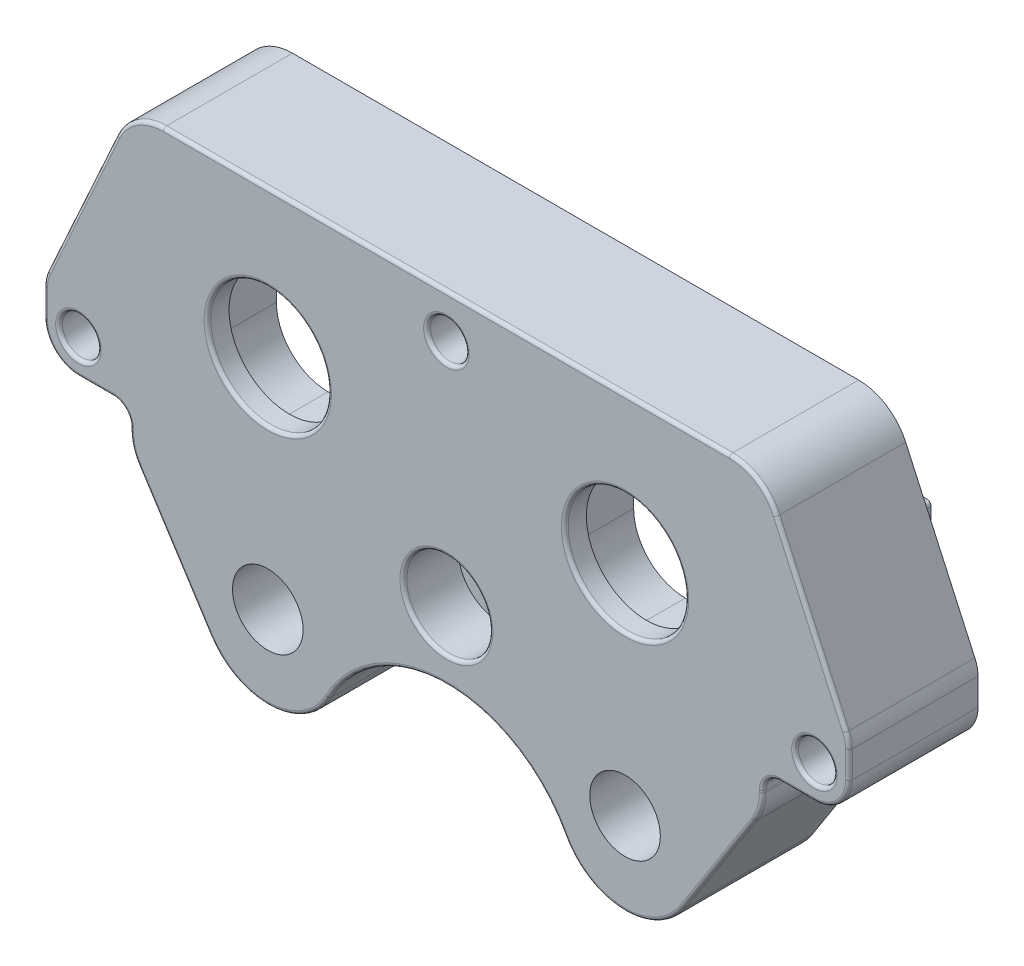
SolidWorks part; units mm, degrees
ref_plane "Front Plane" through (0, 0, 0) normal (0, 0, 1) x (1, 0, 0)
ref_plane "Top Plane" through (0, 0, 0) normal (0, 1, 0) x (1, 0, 0)
ref_plane "Right Plane" through (0, 0, 0) normal (1, 0, 0) x (0, 0, -1)
sketch "Sketch1" plane through (0, 0, 0) normal (0, 0, 1) x (1, 0, 0)
  line L0 (55.5, 15) -> (27.5, 15)
  line L1 (14, 15) -> (-14, 15)
  line L2 (14, 15) -> (14, -15)
  line L3 (14, -15) -> (-14, -15)
  line L4 (-14, 15) -> (-14, -15)
  line L5 (14, 15) -> (-14, -15) construction
  line L6 (14, -15) -> (-14, 15) construction
  line L7 (-16.75, -42) -> (16.75, -42)
  line L8 (-16.75, -42) -> (-16.75, 16)
  line L9 (-16.75, 16) -> (16.75, 16)
  line L10 (16.75, -42) -> (16.75, 16)
  line L11 (55.5, 15) -> (55.5, -15)
  line L12 (55.5, -15) -> (27.5, -15)
  line L13 (27.5, 15) -> (27.5, -15)
  line L14 (55.5, 15) -> (27.5, -15) construction
  line L15 (55.5, -15) -> (27.5, 15) construction
  line L16 (24.75, -42) -> (58.25, -42)
  line L17 (24.75, -42) -> (24.75, 16)
  line L18 (24.75, 16) -> (58.25, 16)
  line L19 (58.25, -42) -> (58.25, 16)
  circle A0 centre (0, 0) radius 19.05 construction
  circle A1 centre (41.5, 0) radius 19.05 construction
  circle A2 centre (20.75, -14.6491) radius 6.35 construction
  circle A3 centre (20.75, -14.6491) radius 41.275 construction
  circle A4 centre (0, 0) radius 7
  circle A5 centre (41.5, 0) radius 7
  circle A6 centre (0, -25.4) radius 4.3
  circle A7 centre (0, -27.1) radius 6.75
  circle A8 centre (41.5, -27.1) radius 6.75
  circle A9 centre (41.5, -25.4) radius 4.3
  point P0 (0, 0)
  point P10 (41.5, 0)
  point P11 (0, -42)
  point P22 (41.5, -42)
  dimension "D6" = 38.1
  dimension "D12" = 38.1
  dimension "D13" = 12.7
  dimension "D15" = 82.55
  dimension "D20" = 14
  dimension "D21" = 14
  dimension "D16" = 8.6
  dimension "D18" = 13.5
  dimension "D1" = 33.5
  dimension "D2" = 28
  dimension "D3" = 30
  dimension "D4" = 16
  dimension "D5" = 58
  dimension "D7" = 33.5
  dimension "D8" = 28
  dimension "D9" = 30
  dimension "D10" = 16
  dimension "D11" = 58
  dimension "D14" = 8
  dimension "D17" = 10.4
  dimension "D19" = 1.7
sketch "Sketch5" plane through (0, 0, 0) normal (0, 0, 1) x (1, 0, 0)
  line L0 (55.5, 15) -> (27.5, -15) construction
  line L1 (14, 15) -> (-14, 15) construction
  line L2 (-16, 17) -> (57.5, 17)
  line L3 (-16, 17) -> (-16, -35.1)
  line L4 (-16, -35.1) -> (57.5, -35.1)
  line L5 (57.5, 17) -> (57.5, -35.1)
  line L6 (-14, 15) -> (-14, -15) construction
  line L7 (55.5, 15) -> (55.5, -15) construction
  line L8 (14, -15) -> (-14, -15) construction
  line L9 (-16, -17) -> (-6.7301, -31.425)
  line L10 (55.5, -15) -> (27.5, -15) construction
  line L11 (57.5, -17) -> (48.2301, -31.425)
  line L12 (-26, -5) -> (-16, 17)
  line L13 (-16, -5) -> (-26, -5)
  line L14 (-16, -5) -> (-16, -13)
  line L15 (-16, -13) -> (-26, -13)
  line L16 (-26, -5) -> (-26, -13)
  line L17 (57.5, -5) -> (67.5, -5)
  line L18 (57.5, -5) -> (57.5, -13)
  line L19 (57.5, -13) -> (67.5, -13)
  line L20 (67.5, -5) -> (67.5, -13)
  line L21 (57.5, 17) -> (67.5, -5)
  circle A0 centre (0, 0) radius 7
  circle A1 centre (41.5, 0) radius 7
  circle A2 centre (20.75, -14.6491) radius 5
  circle A3 centre (0, -25.4) radius 4.1
  circle A4 centre (41.5, -25.4) radius 4.1
  circle A5 centre (41.5, -27.1) radius 6.75
  circle A6 centre (0, -27.1) radius 6.75
  circle A7 centre (0, -27.1) radius 8
  circle A8 centre (41.5, -27.1) radius 8
  circle A9 centre (-22, -9) radius 2.25
  circle A10 centre (20.75, 12) radius 2.25
  circle A11 centre (63.5, -9) radius 2.25
  circle A12 centre (20.75, -38.1651) radius 15.5159
  point P32 (-16, -17)
  point P39 (57.5, -17)
  point P58 (20.75, -22.6491)
  dimension "D1" = 10
  dimension "D2" = 14
  dimension "D3" = 14
  dimension "D4" = 8.2
  dimension "D5" = 8
  dimension "D6" = 13.5
  dimension "D7" = 13.5
  dimension "D18" = 4.5
  dimension "D22" = 4.5
  dimension "D26" = 4.5
  dimension "D8" = 8
  dimension "D9" = 2
  dimension "D10" = 2
  dimension "D11" = 2
  dimension "D12" = 2
  dimension "D13" = 2
  dimension "D14" = 8
  dimension "D15" = 10
  dimension "D16" = 9
  dimension "D17" = 10
  dimension "D19" = 8
  dimension "D20" = 6
  dimension "D21" = 4
  dimension "D23" = 21
  dimension "D24" = 4
  dimension "D25" = 6
extrude "Boss-Extrude5" add sketch "Sketch5" against normal blind 15 contours A8 A5 | A7 A6 | A6 A3 | A5 A4 | A8 L11 L5 L2 L3 L9 A7 L4 A10 A2 A1 A0 | L13 L16 L15 L3 A9 | L20 L17 L5 L19 A11 | L13 L3 L12 | L21 L5 L17 region at (20.75, -3.0463, 0) region at (-19.3333, 2.3333, 0) region at (60.8333, 2.3333, 0) region at (-16.1281, -9, 0) region at (62.5, -5.1281, 0) region at (-2.19, -19.6411, 0) region at (45.2256, -33.9228, 0) region at (34.9409, -27.1, 0) region at (-6.5591, -27.1, 0)
extrude "Cut-Extrude1" cut sketch "Sketch1" along normal blind 12.5 from surface contours L1 L4 L3 L2 A4 | L0 L13 L12 L11 A5 region at (55.0896, 0, 0) region at (13.5896, 0, 0) starting at face at (20.75, -13.3043, -15)
extrude "Cut-Extrude2" cut sketch "Sketch5<3>" along normal blind 2 from surface contours A5 A4 | A6 A3 region at (34.9409, -27.1, 0) region at (-6.5591, -27.1, 0) starting at face at (0, 0, -15)
sketch "Sketch5<3>" plane through (0, 0, 0) normal (0, 0, 1) x (1, 0, 0) same geometry as "Sketch5"
fillet "Fillet1" radius 6 8 edges at (55.5, 15, -8.75) (55.5, -15, -8.75) (27.5, -15, -8.75) (27.5, 15, -8.75) (14, -15, -8.75) (-14, -15, -8.75) (-14, 15, -8.75) (14, 15, -8.75)
fillet "Fillet2" radius 4 4 edges at (-26, -5, -7.5) (-26, -13, -7.5) (67.5, -5, -7.5) (67.5, -13, -7.5)
fillet "Fillet3" radius 6 4 edges at (-16, -17, -7.5) (57.5, -17, -7.5) (-16, 17, -7.5) (57.5, 17, -7.5)
fillet "Fillet4" radius 2 2 edges at (-16, -13, -7.5) (57.5, -13, -7.5)
extrude "Boss-Extrude6" add sketch "Sketch5<4>" along normal blind 8.65 from surface contours A2 region at (20.75, -14.6491, 0) starting at face at (6.75, -27.1, -15)
sketch "Sketch5<4>" plane through (0, 0, 0) normal (0, 0, 1) x (1, 0, 0) same geometry as "Sketch5"
sketch "Sketch6" plane through (0, 0, 0) normal (0, 0, 1) x (1, 0, 0)
  line L1 (-18.3338, -9) -> (-20.1669, -5.825)
  line L2 (-20.1669, -5.825) -> (-23.8331, -5.825)
  line L3 (-23.8331, -5.825) -> (-25.6662, -9)
  line L4 (-25.6662, -9) -> (-23.8331, -12.175)
  line L5 (-23.8331, -12.175) -> (-20.1669, -12.175)
  line L6 (-20.1669, -12.175) -> (-18.3338, -9)
  line L7 (24.287, 11.0352) -> (23.354, 14.5807)
  line L8 (23.354, 14.5807) -> (19.817, 15.5455)
  line L9 (19.817, 15.5455) -> (17.213, 12.9648)
  line L10 (17.213, 12.9648) -> (18.146, 9.4193)
  line L11 (18.146, 9.4193) -> (21.683, 8.4545)
  line L12 (21.683, 8.4545) -> (24.287, 11.0352)
  line L13 (59.8338, -9) -> (61.6669, -12.175)
  line L14 (61.6669, -12.175) -> (65.3331, -12.175)
  line L15 (65.3331, -12.175) -> (67.1662, -9)
  line L16 (67.1662, -9) -> (65.3331, -5.825)
  line L17 (65.3331, -5.825) -> (61.6669, -5.825)
  line L18 (61.6669, -5.825) -> (59.8338, -9)
  circle A0 centre (-22, -9) radius 3.175 construction
  circle A1 centre (20.75, 12) radius 3.175 construction
  circle A2 centre (63.5, -9) radius 3.175 construction
  dimension "D1" = 6.35
  dimension "D2" = 6.35
  dimension "D3" = 6.35
fillet "Fillet5" radius 0.4 30 edges at (-15.3848, 16.0446, 0) (-21.6201, 4.6358, 0) (-25.9093, -5.0196, 0) (-26, -7.4332, 0) (-24.8284, -11.8284, 0) (-20, -13, 0) (-16.5858, -13.5858, 0) (-16, -15.1192, 0) (-15.757, -16.9286, 0) (-10.8889, -24.9535, 0) (0.325, -35.0934, 0) (20.75, -22.6491, 0) (41.175, -35.0934, 0) (52.3889, -24.9535, 0) (57.257, -16.9286, 0) (57.5, -15.1192, 0) (58.0858, -13.5858, 0) (61.5, -13, 0) (66.3284, -11.8284, 0) (67.5, -7.4332, 0) (67.4093, -5.0196, 0) (63.1201, 4.6358, 0) (56.8848, 16.0446, 0) (65.75, -9, 0) (48.5, 0, 0) (25.75, -14.6491, 0) (23, 12, 0) (7, 0, 0) (-19.75, -9, 0) (20.75, 17, 0)
sketch "Sketch7" plane through (0, 0, -15) normal (0, 0, -1) x (-1, 0, 0)
  line L1 (-24.9, 7) -> (-16.6, 7)
  line L2 (-24.9, 7) -> (-24.9, -3)
  line L3 (-24.9, -3) -> (-16.6, -3)
  line L4 (-16.6, 7) -> (-16.6, -3)
  line L5 (-60.05, 7) -> (-58.05, 7)
  line L6 (-60.05, 7) -> (-60.05, -3)
  line L7 (-60.05, -3) -> (-58.05, -3)
  line L8 (-58.05, 7) -> (-58.05, -3)
  line L9 (16.55, 7) -> (18.55, 7)
  line L10 (16.55, 7) -> (16.55, -3)
  line L11 (16.55, -3) -> (18.55, -3)
  line L12 (18.55, 7) -> (18.55, -3)
  circle A0 centre (-20.75, 12) radius 2.25 construction
  circle A1 centre (-63.5, -9) radius 2.25 construction
  circle A2 centre (22, -9) radius 2.25 construction
  point P16 (0, 0)
  dimension "D1" = 4.15
  dimension "D2" = 5.45
  dimension "D3" = 4.15
  dimension "D4" = 10
  dimension "D5" = 5
  dimension "D6" = 10
  dimension "D7" = 2
  dimension "D8" = 5.45
extrude "Boss-Extrude7" add sketch "Sketch7" along normal blind 2
fillet "Fillet6" radius 0.5 25 edges at (-18.55, 2, -15) (20.75, -3, -15) (59.05, -3, -15) (-17.55, 7, -15) (-17.55, -3, -15) (24.9, 2, -15) (16.6, 2, -15) (58.05, 2, -15) (60.05, 2, -15) (-16.55, 7, -16) (-16.55, 2, -17) (-16.55, -3, -16) (-16.55, 2, -15) (-18.55, 7, -16) (-18.55, -3, -16) (16.6, -3, -16) (24.9, -3, -16) (24.9, 7, -16) (16.6, 7, -16) (20.75, 7, -15) (59.05, 7, -15) (60.05, 7, -16) (58.05, 7, -16) (58.05, -3, -16) (60.05, -3, -16)
